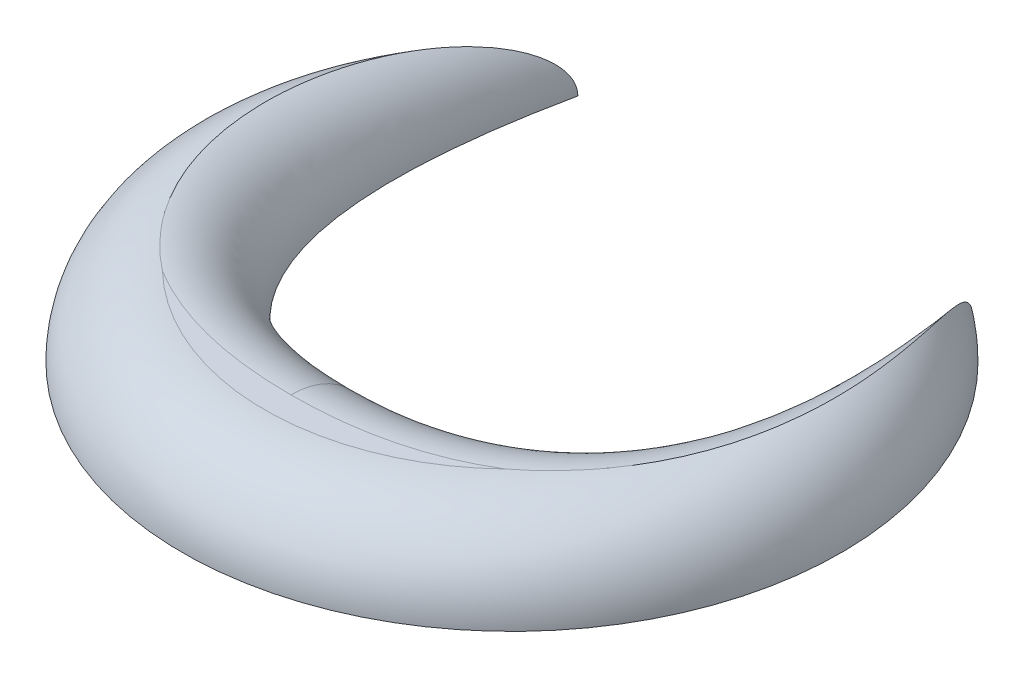
SolidWorks part; units mm, degrees
ref_plane "Front Plane" through (0, 0, 0) normal (0, 0, 1) x (1, 0, 0)
ref_plane "Top Plane" through (0, 0, 0) normal (0, 1, 0) x (1, 0, 0)
ref_plane "Right Plane" through (0, 0, 0) normal (1, 0, 0) x (0, 0, -1)
sketch "Sketch1" plane through (0, 0, 0) normal (0, 1, 0) x (1, 0, 0)
  line L0 (-6, 8) -> (-8.5633, -4.2081) construction
  line L1 (-8.5633, -4.2081) -> (0, -4.2081) construction
  line L2 (0, 10) -> (0, -10) construction
  line L3 (6, 8) -> (8.5633, -4.2081) construction
  line L4 (8.5633, -4.2081) -> (0, -4.2081) construction
  arc A0 (-6, 8) -> (6, 8) centre (0, 0) ccw
  spline S0 degree 2 poles (-6, 8) (-8.5633, -4.2081) (0, -4.2081) knots 0 0 0 1 1 1
  spline S1 degree 2 poles (6, 8) (8.5633, -4.2081) (0, -4.2081) knots 0 0 0 1 1 1
  point P8 (0, 0)
  point P9 (-8.5633, -4.2081)
  point P10 (-5.258, 8.5061)
  dimension "D1" = 20
  dimension "D2" = 12
extrude "Boss-Extrude1" add sketch "Sketch1" along normal blind 2.5
fillet "Fillet1" radius 2.5 3 edges at (0, 2.5, 10)
ref_plane "Plane1" through (0, 0, 10) normal (0, 0, 1) x (1, 0, 0)
sketch "Sketch2" plane through (0, 0, 10) normal (0, 0, 1) x (1, 0, 0)
  line L0 (-10, 0) -> (-10, -20)
  line L1 (-10, 0) -> (10, 0)
  line L2 (0, 0) -> (0, -20) construction
  line L3 (-10, -20) -> (10, -20)
  line L4 (10, 0) -> (10, -20)
  line L5 (6, 0) -> (6, -20)
  line L7 (-6, 0) -> (-6, -20)
  dimension "D1" = 20
  dimension "D2" = 10
  dimension "D3" = 4
